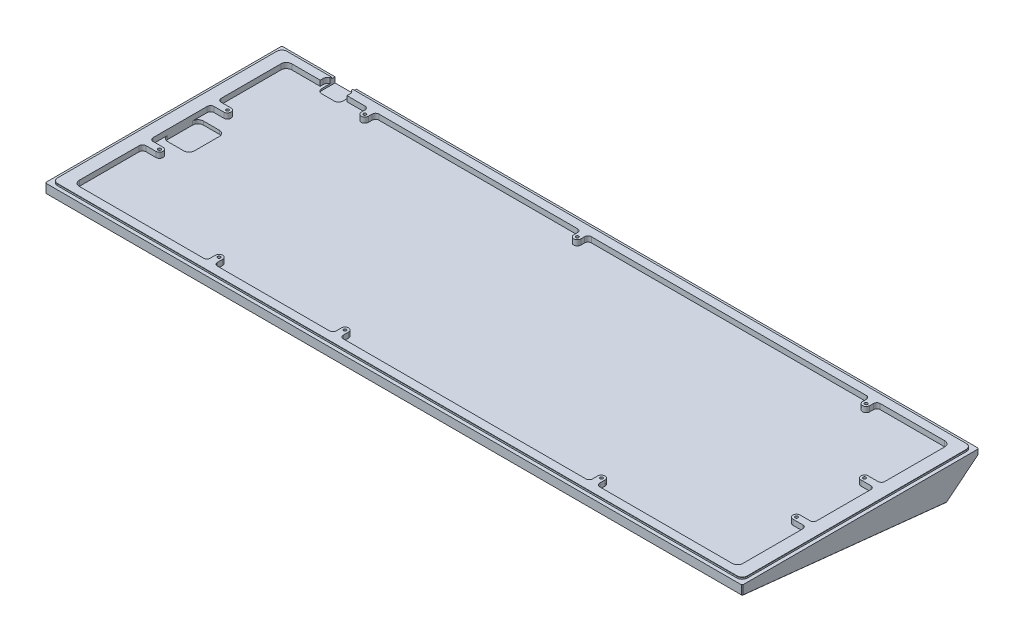
SolidWorks part; units mm, degrees
material "6061-T6 (SS)"
ref_plane "Front Plane" through (0, 0, 0) normal (0, 0, 1) x (1, 0, 0)
ref_plane "Top Plane" through (0, 0, 0) normal (0, 1, 0) x (1, 0, 0)
ref_plane "Right Plane" through (0, 0, 0) normal (1, 0, 0) x (0, 0, -1)
sketch "Sketch1" plane through (0, 0, 0) normal (0, 1, 0) x (1, 0, 0)
  line L1 (0, 0) -> (390.7, 0)
  line L2 (0, 0) -> (0, 132.7)
  line L3 (0, 132.7) -> (390.7, 132.7)
  line L4 (390.7, 0) -> (390.7, 132.7)
  dimension "D1" = 390.7
  dimension "D2" = 132.7
extrude "MainBody" add sketch "Sketch1" along normal blind 18.5
sketch "Sketch2" plane through (0, 18.5, 0) normal (0, 1, 0) x (1, 0, 0)
  line L0 (390.7, 132.7) -> (0, 132.7) construction
  line L1 (2, 130.7) -> (388.7, 130.7)
  line L2 (2, 130.7) -> (2, 2)
  line L3 (2, 2) -> (388.7, 2)
  line L4 (388.7, 130.7) -> (388.7, 2)
  line L5 (0, 132.7) -> (0, 0) construction
  line L7 (0, 132.7) -> (390.7, 132.7)
  line L8 (0, 132.7) -> (0, 0)
  line L9 (0, 0) -> (390.7, 0)
  line L10 (390.7, 132.7) -> (390.7, 0)
  point P4 (195.35, 130.7)
  point P7 (195.35, 132.7)
  point P8 (2, 66.35)
  point P11 (0, 66.35)
  line M5 (0, 132.7) -> (0, 0)
  line M6 (0, 0) -> (390.7, 0)
  line M7 (390.7, 0) -> (390.7, 132.7)
  line M8 (390.7, 132.7) -> (0, 132.7)
  dimension "D1" = 2
  dimension "D2" = 2
extrude "AligmentLip" cut sketch "Sketch2" against normal blind 1 contours L1 L4 L3 L2 M8 M5 M6 M7
sketch "Sketch3" plane through (0, 0, 0) normal (-1, 0, 0) x (0, 0, 1)
  line L0 (-132.7, 14.5) -> (-114.794, 0)
  line L1 (-132.7, 17.5) -> (-132.7, 0) construction
  line L2 (-132.7, 0) -> (0, 0) construction
  line L3 (-114.794, 0) -> (0, 12.0653)
  line L4 (0, 17.5) -> (0, 0) construction
  line L5 (-132.7, 17.5) -> (0, 17.5) construction
  line L7 (-132.7, 17.5) -> (0, 17.5)
  line L8 (-132.7, 17.5) -> (-132.7, 0)
  line L9 (-132.7, 0) -> (0, 0)
  line L10 (0, 17.5) -> (0, 0)
  line M4 (-132.7, 17.5) -> (-132.7, 0)
  line M5 (-132.7, 0) -> (0, 0)
  line M6 (0, 0) -> (0, 17.5)
  dimension "D1" = 6
  dimension "D2" = 135
  dimension "D3" = 3
extrude "TypingAngle" cut sketch "Sketch3" against normal through all contours L0 M4 M5 | L3 M5 M6
sketch "Sketch4" plane through (0, 18.5, 0) normal (0, 1, 0) x (1, 0, 0)
  line L0 (2, 130.7) -> (388.7, 130.7) construction
  line L1 (9.35, 125.9) -> (381.35, 125.9)
  line L2 (9.35, 125.9) -> (9.35, 6.8)
  line L3 (9.35, 6.8) -> (381.35, 6.8)
  line L4 (381.35, 125.9) -> (381.35, 6.8)
  line L5 (2, 130.7) -> (2, 2) construction
  point P4 (195.35, 125.9)
  point P7 (195.35, 130.7)
  point P8 (9.35, 66.35)
  point P11 (2, 66.35)
  dimension "D1" = 372
  dimension "D2" = 119.1
extrude "PCBCutout" cut sketch "Sketch4" against normal blind 3
sketch "Sketch13" plane through (0, 15.5, 0) normal (0, 1, 0) x (1, 0, 0)
  line L0 (9.35, 125.9) -> (9.35, 6.8) construction
  line L1 (9.35, 76.35) -> (24.35, 76.35)
  line L2 (9.35, 76.35) -> (9.35, 56.35)
  line L3 (9.35, 56.35) -> (24.35, 56.35)
  line L4 (24.35, 76.35) -> (24.35, 56.35)
  line L5 (2, 130.7) -> (2, 2) construction
  point P6 (9.35, 66.35)
  point P9 (2, 66.35)
  dimension "D1" = 15
  dimension "D2" = 20
extrude "Cut-Extrude4" cut sketch "Sketch13" against normal blind 2
fillet "Fillet2" radius 3 12 edges at (381.35, 17, -125.9) (388.7, 18, -130.7) (388.7, 18, -2) (381.35, 17, -6.8) (9.35, 17, -6.8) (2, 18, -2) (9.35, 17, -125.9) (2, 18, -130.7) (9.35, 14.5, -56.35) (24.35, 14.5, -56.35) (9.35, 14.5, -76.35) (24.35, 14.5, -76.35)
chamfer "Chamfer1" distance 0.5 angle 45 13 edges at (195.35, 12.0653, 0) (390.7, 16, -132.7) (0, 16, -132.7) (0, 7.25, -123.747) (390.7, 7.25, -123.747) (390.7, 6.0327, -57.397) (390.7, 14.7827, 0) (0, 6.0327, -57.397) (0, 14.7827, 0) (0, 17.5, -66.35) (195.35, 17.5, 0) (390.7, 17.5, -66.35) (195.35, 17.5, -132.7)
chamfer "Chamfer2" distance 0.1 angle 45 8 edges at (388.7, 18.5, -66.35) (387.8213, 18.5, -129.8213) (387.8213, 18.5, -2.8787) (195.35, 18.5, -130.7) (195.35, 18.5, -2) (2.8787, 18.5, -129.8213) (2.8787, 18.5, -2.8787) (2, 18.5, -66.35)
sketch "Sketch17" plane through (0, 11.9335, -1.2543) normal (0, -0.9945, 0.1045) x (1, 0, 0)
  line L0 (198.1, -60.7388) -> (196.1, -60.7388) construction
  line L1 (198.1, -68.7388) -> (196.1, -68.7388)
  line L2 (198.1, -68.7388) -> (198.1, -52.7388)
  line L3 (198.1, -52.7388) -> (196.1, -52.7388)
  line L4 (196.1, -68.7388) -> (196.1, -52.7388)
  line L5 (202.6, -61.2388) -> (200.6, -61.2388)
  line L6 (202.6, -61.2388) -> (202.6, -48.7388)
  line L7 (202.6, -48.7388) -> (200.6, -48.7388)
  line L8 (200.6, -61.2388) -> (200.6, -48.7388)
  line L9 (193.6, -61.2388) -> (191.6, -61.2388)
  line L10 (193.6, -61.2388) -> (193.6, -53.2388)
  line L11 (193.6, -53.2388) -> (191.6, -53.2388)
  line L12 (191.6, -61.2388) -> (191.6, -53.2388)
  line L13 (190.1, -61.2388) -> (188.1, -61.2388)
  line L14 (190.1, -61.2388) -> (190.1, -53.2388)
  line L15 (190.1, -53.2388) -> (188.1, -53.2388)
  line L16 (188.1, -61.2388) -> (188.1, -53.2388)
  line L17 (186.6, -61.2388) -> (184.6, -61.2388)
  line L18 (186.6, -61.2388) -> (186.6, -53.2388)
  line L19 (186.6, -53.2388) -> (184.6, -53.2388)
  line L20 (184.6, -61.2388) -> (184.6, -53.2388)
  line L25 (202.6, -61.2388) -> (188.1, -61.2388) construction
  line L26 (390.2, -114.1651) -> (0.5, -114.1651) construction
  line L27 (194.1, -64.7388) -> (198.1, -64.7388)
  line L28 (194.1, -62.7388) -> (198.1, -62.7388)
  line L29 (390.7, 1.2612) -> (0, 1.2612) construction
  line L31 (206.1, -53.2388) -> (204.1, -53.2388)
  line L32 (206.1, -53.2388) -> (206.1, -48.7388)
  line L33 (206.1, -48.7388) -> (204.1, -48.7388)
  line L34 (204.1, -53.2388) -> (204.1, -48.7388)
  circle A0 centre (201.6, -63.7388) radius 1
  circle A2 centre (194.1, -63.7388) radius 1
  circle A3 centre (197.1, -67.7388) radius 1
  circle A4 centre (197.1, -53.7388) radius 1
  circle A5 centre (201.6, -60.2388) radius 1
  circle A6 centre (201.6, -49.7388) radius 1
  circle A7 centre (205.1, -52.2388) radius 1
  circle A8 centre (205.1, -49.7388) radius 1
  circle A9 centre (192.6, -60.2388) radius 1
  circle A10 centre (192.6, -54.2388) radius 1
  circle A11 centre (189.1, -60.2388) radius 1
  circle A12 centre (189.1, -54.2388) radius 1
  circle A13 centre (185.6, -60.2388) radius 1
  circle A14 centre (185.6, -54.2388) radius 1
  point P28 (195.35, -61.2388)
  point P29 (201.6, -61.2388)
  point P33 (195.35, -114.1651)
  point P44 (197.1, -68.7388)
  dimension "D12" = 2
  dimension "D13" = 12.5
  dimension "D16" = 2
  dimension "D1" = 16
  dimension "D2" = 2
  dimension "D3" = 0
  dimension "D4" = 2.5
  dimension "D5" = 2.5
  dimension "D6" = 1.5
  dimension "D7" = 1.5
  dimension "D8" = 8
  dimension "D9" = 0.5
  dimension "D10" = 1.5
  dimension "D11" = 2.5
  dimension "D14" = 4.5
  dimension "D15" = 50
  dimension "D17" = 2
  dimension "D18" = 3
  dimension "D19" = 11
extrude "Cut-Extrude5" cut sketch "Sketch17" against normal blind 1 contours A7 | A8 L34 A7 L32 | A8 | A6 | A6 L8 A5 L6 | A5 | A4 | A4 L4 L28 L2 | L28 L4 L27 L2 | A3 L2 L27 L4 | A3 | A2 L27 L4 L28 | A2 | A0 | A9 | A10 L12 A9 L10 | A10 | A12 L16 A11 L14 | A11 | A12 | A14 | A14 L20 A13 L18 | A13
sketch "Sketch18" plane through (0, 0, -132.7) normal (0, 0, -1) x (-1, 0, 0)
  line L0 (-385.7, 18.5) -> (-5, 18.5) construction
  line L1 (-41.8, 18.5) -> (-29.8, 18.5)
  line L2 (-41.8, 18.5) -> (-41.8, 14.5)
  line L3 (-41.8, 14.5) -> (-29.8, 14.5)
  line L4 (-29.8, 18.5) -> (-29.8, 14.5)
  line L6 (-390.2, 14.5) -> (-0.5, 14.5) construction
  line L7 (0, 17.5) -> (0, 14.7385) construction
  point P6 (-35.8, 18.5)
  dimension "D1" = 35.8
  dimension "D3" = 12
extrude "Cut-Extrude6" cut sketch "Sketch18" against normal blind 10
sketch "Sketch12" plane through (0, 18.5, 0) normal (0, 1, 0) x (1, 0, 0)
  line L0 (381.35, 125.9) -> (9.35, 125.9) construction
  line L1 (28.3, 125.9) -> (43.3, 125.9)
  line L2 (28.3, 125.9) -> (28.3, 129.85)
  line L3 (28.3, 129.85) -> (43.3, 129.85)
  line L4 (43.3, 125.9) -> (43.3, 129.85)
  line L6 (390.7, 132.7) -> (0, 132.7) construction
  line L7 (41.8, 132.7) -> (29.8, 132.7) construction
  point P6 (35.8, 129.85)
  point P11 (35.8, 132.7)
  dimension "D1" = 15
  dimension "D2" = 2.85
extrude "Cut-Extrude3" cut sketch "Sketch12" against normal up to surface (3 mm away) up to face at (92.04, 15.5, -77.94)
fillet "Fillet1" radius 2.5 4 edges at (43.3, 17, -129.85) (28.3, 17, -129.85) (41.8, 15, -122.7) (29.8, 15, -122.7)
sketch "Sketch19" plane through (0, 15.5, 0) normal (0, 1, 0) x (1, 0, 0)
  line L1 (195.35, 0) -> (195.35, 132.7) construction
  line L6 (378.35, 125.9) -> (43.3, 125.9) construction
  line L7 (55.3, 121.9) -> (59.3, 121.9)
  line L8 (55.3, 121.9) -> (55.3, 125.9)
  line L9 (55.3, 125.9) -> (59.3, 125.9)
  line L10 (59.3, 121.9) -> (59.3, 125.9)
  line L11 (378.35, 125.9) -> (43.3, 125.9) construction
  line L12 (174.4, 121.9) -> (178.4, 121.9)
  line L13 (174.4, 121.9) -> (174.4, 125.9)
  line L14 (174.4, 125.9) -> (178.4, 125.9)
  line L15 (178.4, 121.9) -> (178.4, 125.9)
  line L16 (336.3, 121.9) -> (340.3, 121.9)
  line L17 (336.3, 121.9) -> (336.3, 125.9)
  line L18 (336.3, 125.9) -> (340.3, 125.9)
  line L19 (340.3, 121.9) -> (340.3, 125.9)
  line L20 (381.35, 9.8) -> (381.35, 122.9) construction
  line L21 (373.9, 87.4) -> (381.35, 87.4)
  line L22 (373.9, 87.4) -> (373.9, 83.4)
  line L23 (373.9, 83.4) -> (381.35, 83.4)
  line L24 (381.35, 87.4) -> (381.35, 83.4)
  line L25 (12.35, 6.8) -> (378.35, 6.8) construction
  line L26 (373.9, 49.3) -> (381.35, 49.3)
  line L27 (373.9, 49.3) -> (373.9, 45.3)
  line L28 (373.9, 45.3) -> (381.35, 45.3)
  line L29 (381.35, 49.3) -> (381.35, 45.3)
  line L30 (298.2, 11.6) -> (302.2, 11.6)
  line L31 (298.2, 11.6) -> (298.2, 6.8)
  line L32 (298.2, 6.8) -> (302.2, 6.8)
  line L33 (302.2, 11.6) -> (302.2, 6.8)
  line L34 (12.35, 6.8) -> (378.35, 6.8) construction
  line L35 (158.5, 11.6) -> (154.5, 11.6)
  line L36 (158.5, 11.6) -> (158.5, 6.8)
  line L37 (158.5, 6.8) -> (154.5, 6.8)
  line L38 (154.5, 11.6) -> (154.5, 6.8)
  line L39 (9.35, 59.35) -> (9.35, 9.8) construction
  line L40 (87.9, 11.6) -> (83.9, 11.6)
  line L41 (87.9, 11.6) -> (87.9, 6.8)
  line L42 (87.9, 6.8) -> (83.9, 6.8)
  line L43 (83.9, 11.6) -> (83.9, 6.8)
  line L44 (16.8, 49.3) -> (9.35, 49.3)
  line L45 (16.8, 49.3) -> (16.8, 45.3)
  line L46 (16.8, 45.3) -> (9.35, 45.3)
  line L47 (9.35, 49.3) -> (9.35, 45.3)
  line L48 (9.35, 122.9) -> (9.35, 9.8) construction
  line L49 (16.8, 87.4) -> (9.35, 87.4)
  line L50 (16.8, 87.4) -> (16.8, 83.4)
  line L51 (16.8, 83.4) -> (9.35, 83.4)
  line L52 (9.35, 87.4) -> (9.35, 83.4)
  line L53 (390.2, 132.7) -> (41.8, 132.7) construction
  line L54 (0, 132.2) -> (0, 0.5) construction
  line L55 (0.5, 0) -> (390.2, 0) construction
  circle A0 centre (57.3, 121.9) radius 2
  circle A1 centre (176.4, 121.9) radius 2
  circle A2 centre (338.3, 121.9) radius 2
  circle A3 centre (16.8, 85.4) radius 2
  circle A4 centre (16.8, 47.3) radius 2
  circle A5 centre (85.9, 11.6) radius 2
  circle A6 centre (156.5, 11.6) radius 2
  circle A7 centre (300.2, 11.6) radius 2
  circle A8 centre (373.9, 85.4) radius 2
  circle A9 centre (373.9, 47.3) radius 2
  point P19 (0, 0)
  point P21 (0, 0)
  point P22 (0, 0)
  point P84 (0, 0)
  dimension "D2" = 4
  dimension "D6" = 4
  dimension "D12" = 4
  dimension "D3" = 57.3
  dimension "D4" = 119.1
  dimension "D5" = 161.9
  dimension "D7" = 40.5
  dimension "D8" = 38.1
  dimension "D9" = 36.5
  dimension "D10" = 110.3
  dimension "D11" = 28.6
  dimension "D13" = 70.6
  dimension "D14" = 143.7
  dimension "D15" = 10.8
extrude "Boss-Extrude1" add sketch "Sketch19" along normal up to surface (3 mm away) contours L46 L47 L44 L45 | L51 L52 L49 L50 | A4 | A3 | L10 L9 L8 L7 | A0 | L15 L14 L13 L12 | A1 | L19 L18 L17 L16 | A2 | L21 L24 L23 L22 | A8 | L26 L29 L28 L27 | A9 | L33 L32 L31 L30 | A7 | L36 L37 L38 L35 | A6 | L41 L42 L43 L40 | A5 up to face at (142.1667, 18.5, -87.0777)
fillet "Fillet3" radius 1.9 20 edges at (83.9, 17, -6.8) (87.9, 17, -6.8) (158.5, 17, -6.8) (154.5, 17, -6.8) (298.2, 17, -6.8) (302.2, 17, -6.8) (381.35, 17, -45.3) (381.35, 17, -49.3) (381.35, 17, -87.4) (381.35, 17, -83.4) (336.3, 17, -125.9) (340.3, 17, -125.9) (178.4, 17, -125.9) (174.4, 17, -125.9) (59.3, 17, -125.9) (55.3, 17, -125.9) (9.35, 17, -87.4) (9.35, 17, -49.3) (9.35, 17, -45.3) (9.35, 17, -83.4)
sketch "Sketch20" plane through (0, 18.5, 0) normal (0, 1, 0) x (1, 0, 0)
  point P0 (16.8, 47.3)
  point P1 (16.8, 85.4)
  point P3 (85.9, 11.6)
  point P5 (156.5, 11.6)
  point P7 (300.2, 11.6)
  point P9 (373.9, 47.3)
  point P11 (373.9, 85.4)
  point P13 (338.3, 121.9)
  point P15 (176.4, 121.9)
  point P17 (57.3, 121.9)
  point P19 (0, 0)
  point P21 (0, 0)
  point P22 (0, 0)
  point P23 (0, 0)
  point P24 (0, 0)
  point P25 (0, 0)
  point P26 (0, 0)
  point P27 (0, 0)
  point P28 (0, 0)
  point P29 (0, 0)
hole_wizard "M2x0.4 Tapped Hole1" positions "3DSketch3" profile "Sketch22" tap size "M2x0.4" standard "ANSI Metric"
sketch3d "3DSketch3"
  point P0 (57.3, 18.5, -121.9)
  point P3 (176.4, 18.5, -121.9)
  point P6 (16.8, 18.5, -47.3)
  point P9 (16.8, 18.5, -85.4)
  point P12 (85.9, 18.5, -11.6)
  point P15 (156.5, 18.5, -11.6)
  point P18 (300.2, 18.5, -11.6)
  point P21 (373.9, 18.5, -47.3)
  point P24 (373.9, 18.5, -85.4)
  point P27 (338.3, 18.5, -121.9)
sketch "Sketch22" plane through (57.3, 18.5, -121.9) normal (1, 0, 0) x (0, 0, 1)
  line L0 (0, 0) -> (0, 4.4807)
  line L1 (0, 4.4807) -> (0.8, 4)
  line L2 (0.8, 4) -> (0.8, 0)
  line L5 (0.8, 0) -> (0, 0)
  line L10 (0, 4.4807) -> (-0.8, 4) construction
  line L11 (0, -6.35) -> (0, 107.95) construction
  dimension "Tap Drill Dia." = 1.6
  dimension "Tap Drill Depth" = 4
  dimension "Drill Angle" = 118
cosmetic thread "Hole Thread1" parameters "D1"=4, "D2"=2
cosmetic thread "Hole Thread2" parameters "D1"=4, "D2"=2
cosmetic thread "Hole Thread3" parameters "D1"=4, "D2"=2
cosmetic thread "Hole Thread4" parameters "D1"=4, "D2"=2
cosmetic thread "Hole Thread5" parameters "D1"=4, "D2"=2
cosmetic thread "Hole Thread6" parameters "D1"=4, "D2"=2
cosmetic thread "Hole Thread7" parameters "D1"=4, "D2"=2
cosmetic thread "Hole Thread8" parameters "D1"=4, "D2"=2
cosmetic thread "Hole Thread9" parameters "D1"=4, "D2"=2
cosmetic thread "Hole Thread10" parameters "D1"=4, "D2"=2
